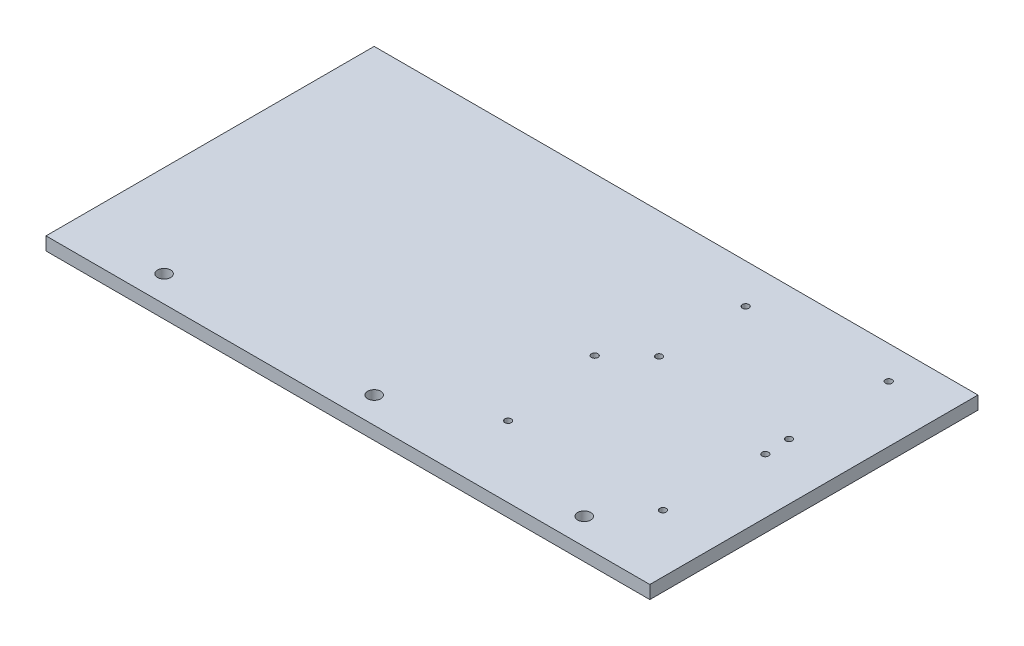
SolidWorks part; units mm, degrees
ref_plane "Front Plane" through (0, 0, 0) normal (0, 0, 1) x (1, 0, 0)
ref_plane "Top Plane" through (0, 0, 0) normal (0, 1, 0) x (1, 0, 0)
ref_plane "Right Plane" through (0, 0, 0) normal (1, 0, 0) x (0, 0, -1)
sketch "Sketch1" plane through (0, 0, 0) normal (0, 1, 0) x (1, 0, 0)
  line L1 (0, 0) -> (292.1, 0)
  line L2 (0, 0) -> (0, 158.75)
  line L3 (0, 158.75) -> (292.1, 158.75)
  line L4 (292.1, 0) -> (292.1, 158.75)
  dimension "D1" = 292.1
  dimension "D2" = 158.75
extrude "Boss-Extrude1" add sketch "Sketch1" along normal blind 6.35
sketch "Sketch2" plane through (0, 6.35, 0) normal (0, 1, 0) x (1, 0, 0)
  line L0 (0, 25.4) -> (292.1, 25.4) construction
  line L1 (0, 12.7) -> (292.1, 12.7) construction
  line L2 (146.05, 0) -> (146.05, 158.75) construction
  line L4 (0, 158.75) -> (0, 0)
  line L5 (0, 0) -> (292.1, 0)
  line L6 (292.1, 0) -> (292.1, 158.75)
  line L7 (292.1, 158.75) -> (0, 158.75)
  line L8 (0, 158.75) -> (0, 0) construction
  line L9 (0, 0) -> (292.1, 0) construction
  line L10 (292.1, 0) -> (292.1, 158.75) construction
  line L11 (292.1, 158.75) -> (0, 158.75) construction
  circle A0 centre (146.05, 12.7) radius 3.175
  circle A1 centre (247.65, 12.7) radius 3.175
  circle A2 centre (44.45, 12.7) radius 3.175
  dimension "D6" = 6.35
  dimension "D7" = 6.35
  dimension "D8" = 6.35
  dimension "D2" = 25.4
  dimension "D3" = 12.7
  dimension "D4" = 101.6
  dimension "D5" = 101.6
  dimension "D1" = 0
extrude "Cut-Extrude2" cut sketch "Sketch2" against normal blind 6.35
sketch "Sketch4" plane through (0, 6.35, 0) normal (0, 1, 0) x (1, 0, 0)
  line L4 (279.4, 85.09) -> (177.8, 85.09)
  line L5 (177.8, 85.09) -> (177.8, 31.75)
  line L6 (177.8, 31.75) -> (279.4, 31.75)
  line L7 (279.4, 31.75) -> (279.4, 85.09)
  line L8 (279.4, 85.09) -> (177.8, 85.09) construction
  line L9 (177.8, 85.09) -> (177.8, 31.75) construction
  line L10 (177.8, 31.75) -> (279.4, 31.75) construction
  line L11 (279.4, 31.75) -> (279.4, 85.09) construction
  circle A1 centre (182.88, 82.55) radius 1.5875
  circle A2 centre (182.88, 82.55) radius 1.5875
  circle A3 centre (189.23, 34.29) radius 1.5875
  circle A4 centre (189.23, 34.29) radius 1.5875
  circle A5 centre (265.43, 82.55) radius 1.5875
  circle A6 centre (265.43, 82.55) radius 1.5875
  circle A7 centre (264.16, 34.29) radius 1.5875
  circle A8 centre (264.16, 34.29) radius 1.5875
  circle A9 centre (264.795, 142.875) radius 1.5875
  circle A10 centre (264.795, 142.875) radius 1.5875
  circle A11 centre (264.795, 94.615) radius 1.5875
  circle A12 centre (264.795, 94.615) radius 1.5875
  circle A13 centre (198.755, 97.79) radius 1.5875
  circle A14 centre (198.755, 97.79) radius 1.5875
  circle A15 centre (198.755, 139.7) radius 1.5875
  circle A16 centre (198.755, 139.7) radius 1.5875
  dimension "D1" = 0
  dimension "D2" = 0
  dimension "D3" = 0
  dimension "D4" = 0
  dimension "D5" = 0
  dimension "D6" = 0
  dimension "D7" = 0
  dimension "D8" = 0
  dimension "D9" = 0
extrude "Cut-Extrude3" cut sketch "Sketch4" against normal through all
equation "\"D5@Sketch2\"=\"D4@Sketch2\""
equation "\"D7@Sketch2\"=\"D6@Sketch2\""
equation "\"D8@Sketch2\"=\"D7@Sketch2\""
